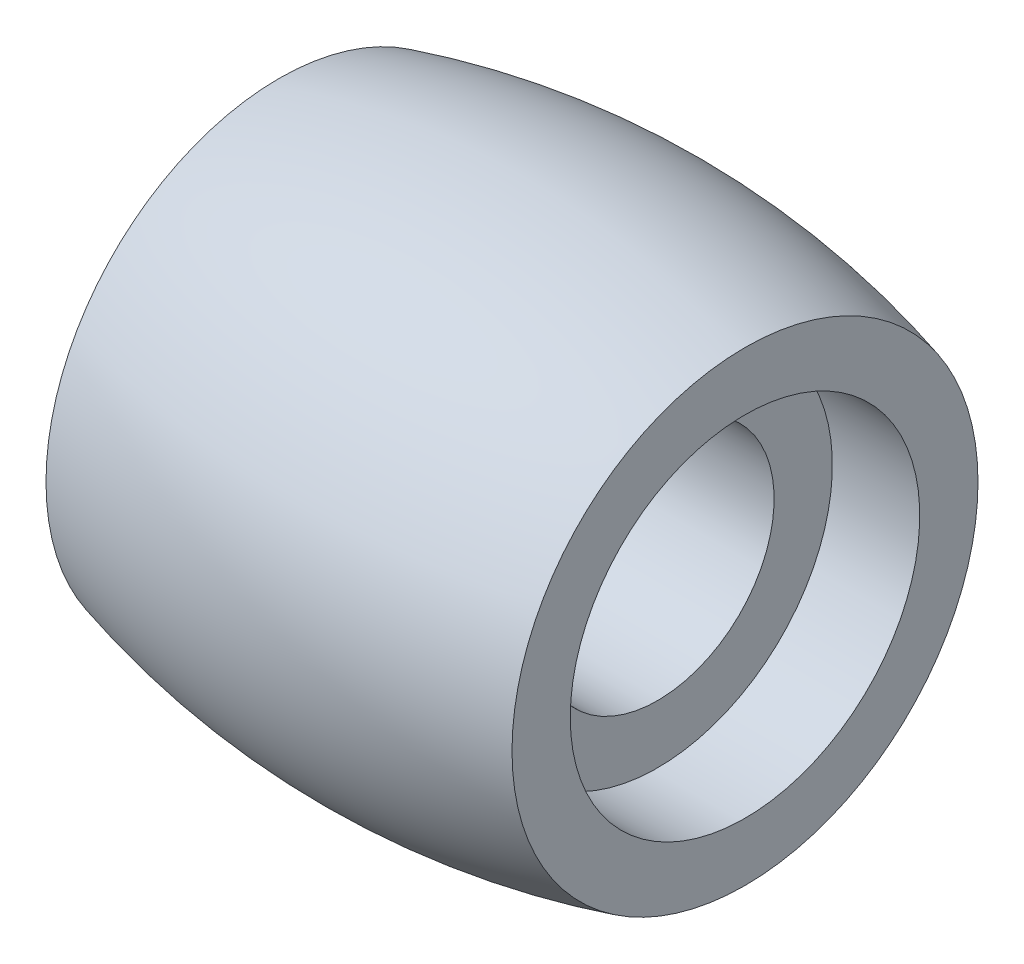
SolidWorks part; units mm, degrees
ref_plane "Front Plane" through (0, 0, 0) normal (0, 0, 1) x (1, 0, 0)
ref_plane "Top Plane" through (0, 0, 0) normal (0, 1, 0) x (1, 0, 0)
ref_plane "Right Plane" through (0, 0, 0) normal (1, 0, 0) x (0, 0, -1)
sketch "Sketch2" plane through (0, 0, 0) normal (0, 0, 1) x (1, 0, 0)
  line L0 (0, 6.5859) -> (0, -8.2148) construction
  line L1 (-8.918, 0) -> (11.5313, 0) construction
  line L2 (-2.5, 2) -> (2.5, 2)
  line L3 (2.5, 2) -> (2.5, 3)
  line L4 (2.5, 3) -> (4, 3)
  line L5 (4, 3) -> (4, 4)
  line L6 (-4, 3) -> (-4, 4)
  line L7 (-2.5, 3) -> (-4, 3)
  line L8 (-2.5, 2) -> (-2.5, 3)
  arc A0 (-4, 4) -> (4, 4) centre (0, -10.4568) cw
  point P18 (0, 2)
  dimension "D6" = 15
  dimension "1.5" = 2
  dimension "D2" = 1.5
  dimension "2.9" = 3
  dimension "D4" = 4
  dimension "D5" = 4
revolve "Revolve1" add sketch "Sketch2" angle 360 about L1
